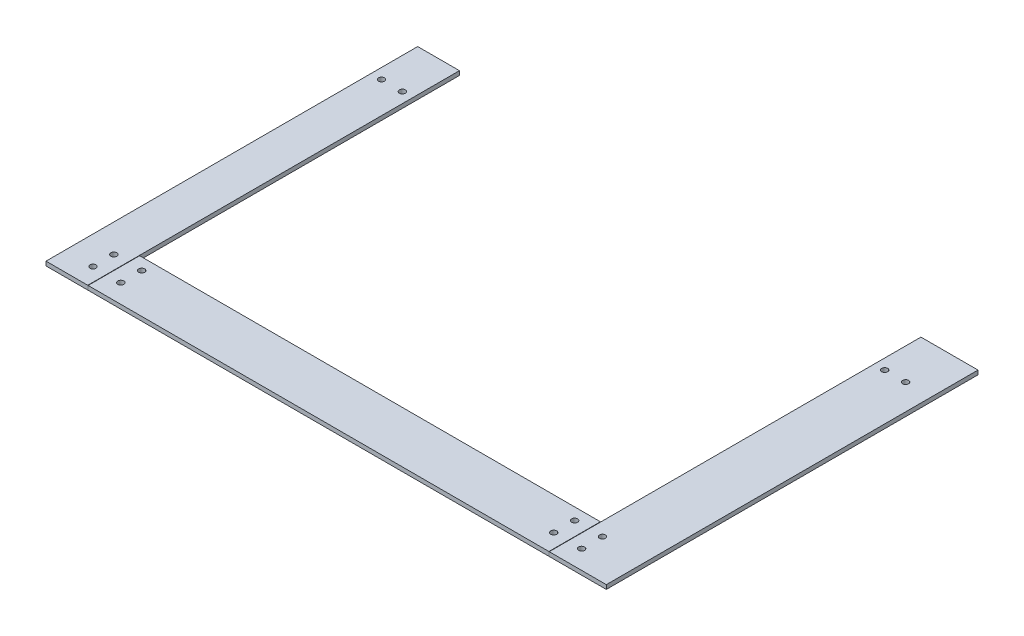
SolidWorks part; units mm, degrees
ref_plane "Front Plane" through (0, 0, 0) normal (0, 0, 1) x (1, 0, 0)
ref_plane "Top Plane" through (0, 0, 0) normal (0, 1, 0) x (1, 0, 0)
ref_plane "Right Plane" through (0, 0, 0) normal (1, 0, 0) x (0, 0, -1)
sketch "Sketch1" plane through (0, 0, 0) normal (0, 1, 0) x (1, 0, 0)
  line L1 (165.75, -135.5) -> (206.75, -135.5)
  line L2 (165.75, -135.5) -> (165.75, 131.5)
  line L3 (165.75, 131.5) -> (206.75, 131.5)
  line L4 (206.75, -135.5) -> (206.75, 131.5)
  line L5 (165.75, -135.5) -> (206.75, 131.5) construction
  line L6 (165.75, 131.5) -> (206.75, -135.5) construction
  point P0 (186.25, -2)
  dimension "D1" = 267
  dimension "D2" = 41
  dimension "D3" = 165.75
  dimension "D4" = 2
extrude "Boss-Extrude1" add sketch "Sketch1" along normal blind 3
sketch "Sketch2" plane through (0, 0, 0) normal (0, 1, 0) x (1, 0, 0)
  line L1 (-195.75, -135.5) -> (-165.75, -135.5)
  line L2 (-195.75, -135.5) -> (-195.75, 131.5)
  line L3 (-195.75, 131.5) -> (-165.75, 131.5)
  line L4 (-165.75, -135.5) -> (-165.75, 131.5)
  line L5 (-195.75, -135.5) -> (-165.75, 131.5) construction
  line L6 (-195.75, 131.5) -> (-165.75, -135.5) construction
  point P0 (-180.75, -2)
  dimension "D1" = 30
  dimension "D2" = 267
  dimension "D3" = 2
  dimension "D4" = 165.75
extrude "Boss-Extrude2" add sketch "Sketch2" along normal blind 3 separate body
sketch "Sketch3" plane through (0, 0, 0) normal (0, 1, 0) x (1, 0, 0)
  line L0 (-195.75, -135.5) -> (-165.75, -135.5) construction
  line L1 (-165.5, -135.5) -> (165.5, -135.5)
  line L2 (-165.5, -135.5) -> (-165.5, -98.5)
  line L3 (-165.5, -98.5) -> (165.5, -98.5)
  line L4 (165.5, -135.5) -> (165.5, -98.5)
  line L5 (-165.5, -135.5) -> (165.5, -98.5) construction
  line L6 (-165.5, -98.5) -> (165.5, -135.5) construction
  point P0 (0, -117)
  dimension "D1" = 331
  dimension "D2" = 37
extrude "Boss-Extrude3" add sketch "Sketch3" along normal blind 3 separate body
hole_wizard "M4 Clearance Hole1" positions "Sketch5" profile "Sketch6" hole size "M4" standard "ANSI Metric" end condition through all
sketch "Sketch5" plane through (0, 3, 0) normal (0, 1, 0) x (1, 0, 0)
  line L1 (-175.5, -122) -> (-155.5, -122)
  line L2 (-175.5, -122) -> (-175.5, -107)
  line L3 (-175.5, -107) -> (-155.5, -107)
  line L4 (-155.5, -122) -> (-155.5, -107)
  line L5 (-175.5, -122) -> (-155.5, -107) construction
  line L6 (-175.5, -107) -> (-155.5, -122) construction
  line L9 (-173.25, 98) -> (-188.25, 98)
  line L11 (-180.75, 131.5) -> (-180.75, 98)
  line L12 (-165.75, 131.5) -> (-195.75, 131.5) construction
  line L13 (165.5, -98.5) -> (-165.5, -98.5) construction
  point P2 (-155.5, -107)
  point P45 (-175.5, -122)
  point P46 (-175.5, -107)
  point P47 (-155.5, -122)
  point P65 (-188.25, 98)
  point P67 (-173.25, 98)
  point P84 (-165.5, -114.5)
  dimension "D1" = 15
  dimension "D2" = 20
  dimension "D3" = 15
  dimension "D4" = 33.5
  dimension "D5" = 16
sketch "Sketch6" plane through (-155.5, 3, 107) normal (1, 0, 0) x (0, 0, 1)
  line L0 (0, 0) -> (0, 3)
  line L1 (0, 3) -> (2.15, 3)
  line L2 (2.15, 3) -> (2.15, 0)
  line L5 (2.15, 0) -> (0, 0)
  line L11 (0, -6.35) -> (0, 107.95) construction
  dimension "Thru Hole Dia." = 4.3
  dimension "Thru Hole Depth" = 3
mirror "Mirror1" about plane through (0, 0, 0) normal (1, 0, 0) of "M4 Clearance Hole1"
